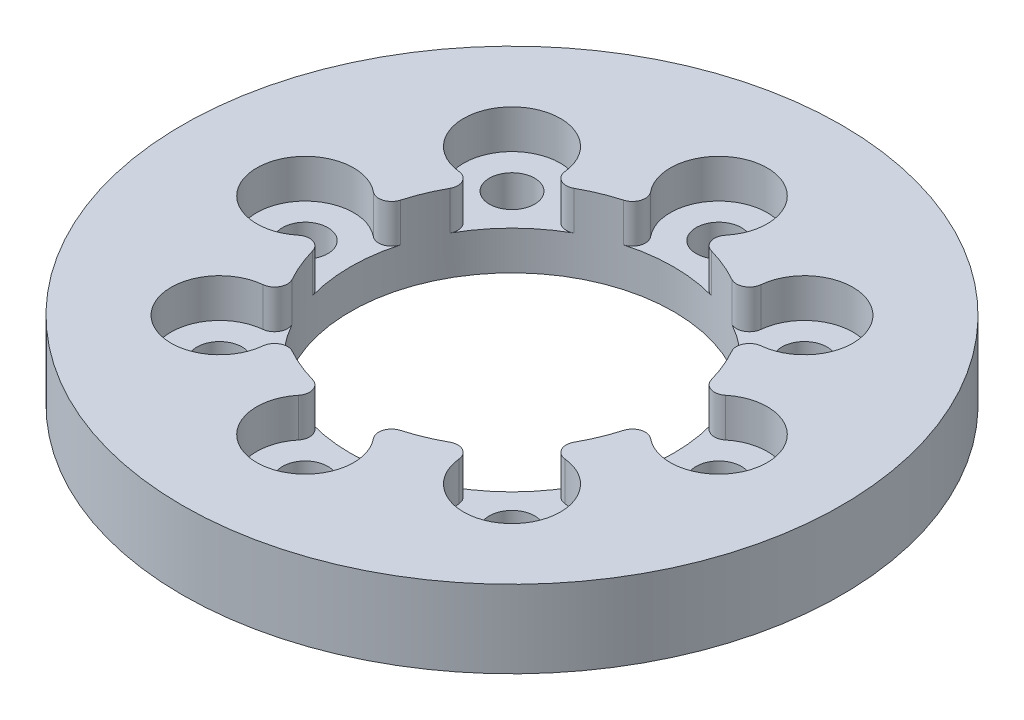
SolidWorks part; units mm, degrees
ref_plane "Front Plane" through (0, 0, 0) normal (0, 0, 1) x (1, 0, 0)
ref_plane "Top Plane" through (0, 0, 0) normal (0, 1, 0) x (1, 0, 0)
ref_plane "Right Plane" through (0, 0, 0) normal (1, 0, 0) x (0, 0, -1)
sketch "Sketch1" plane through (0, 0, 0) normal (0, 1, 0) x (1, 0, 0)
  circle A0 centre (0, 0) radius 25.5
  circle A1 centre (0, 0) radius 12.5
  circle A2 centre (0, 16) radius 1.75
  circle A3 centre (11.3137, 11.3137) radius 1.75
  circle A4 centre (16, 0) radius 1.75
  circle A5 centre (11.3137, -11.3137) radius 1.75
  circle A6 centre (0, -16) radius 1.75
  circle A7 centre (-11.3137, -11.3137) radius 1.75
  circle A8 centre (-16, 0) radius 1.75
  circle A9 centre (-11.3137, 11.3137) radius 1.75
  point P22 (0, 0)
  dimension "D1" = 25
  dimension "D2" = 51
  dimension "D4" = 3.5
  dimension "D3" = 16
  dimension "D5" = 8
extrude "Boss-Extrude1" add sketch "Sketch1" along normal blind 6
sketch "Sketch2" plane through (0, 6, 0) normal (0, 1, 0) x (1, 0, 0)
  circle A0 centre (-11.3137, 11.3137) radius 3.75
  circle A1 centre (-11.3137, 11.3137) radius 1.75
  circle A2 centre (-11.3137, 11.3137) radius 1.75
  circle A3 centre (-11.3137, -11.3137) radius 1.75
  circle A4 centre (-11.3137, -11.3137) radius 1.75
  circle A5 centre (11.3137, -11.3137) radius 1.75
  circle A6 centre (11.3137, -11.3137) radius 1.75
  circle A7 centre (11.3137, 11.3137) radius 1.75
  circle A8 centre (11.3137, 11.3137) radius 1.75
  circle A9 centre (0, 16) radius 1.75
  circle A10 centre (0, 16) radius 1.75
  circle A11 centre (16, 0) radius 1.75
  circle A12 centre (16, 0) radius 1.75
  circle A13 centre (0, -16) radius 1.75
  circle A14 centre (0, -16) radius 1.75
  circle A15 centre (-16, 0) radius 1.75
  circle A16 centre (-16, 0) radius 1.75
  circle A17 centre (-11.3137, -11.3137) radius 3.75
  circle A18 centre (11.3137, -11.3137) radius 3.75
  circle A19 centre (11.3137, 11.3137) radius 3.75
  circle A20 centre (0, 16) radius 3.75
  circle A21 centre (16, 0) radius 3.75
  circle A22 centre (0, -16) radius 3.75
  circle A23 centre (-16, 0) radius 3.75
  dimension "D1" = 0
  dimension "D2" = 0
  dimension "D3" = 0
  dimension "D4" = 0
  dimension "D5" = 0
  dimension "D6" = 0
  dimension "D7" = 0
  dimension "D8" = 0
  dimension "D9" = 2
extrude "Cut-Extrude1" cut sketch "Sketch2" against normal blind 3
fillet "Fillet1" radius 1 16 edges at (7.9583, 4.5, -9.6393) (-12.4434, 4.5, -1.1886) (-1.1886, 4.5, -12.4434) (1.1886, 4.5, -12.4434) (9.6393, 4.5, -7.9583) (12.4434, 4.5, -1.1886) (12.4434, 4.5, 1.1886) (9.6393, 4.5, 7.9583) (7.9583, 4.5, 9.6393) (-7.9583, 4.5, -9.6393) (-9.6393, 4.5, -7.9583) (1.1886, 4.5, 12.4434) (-1.1886, 4.5, 12.4434) (-12.4434, 4.5, 1.1886) (-7.9583, 4.5, 9.6393) (-9.6393, 4.5, 7.9583)
